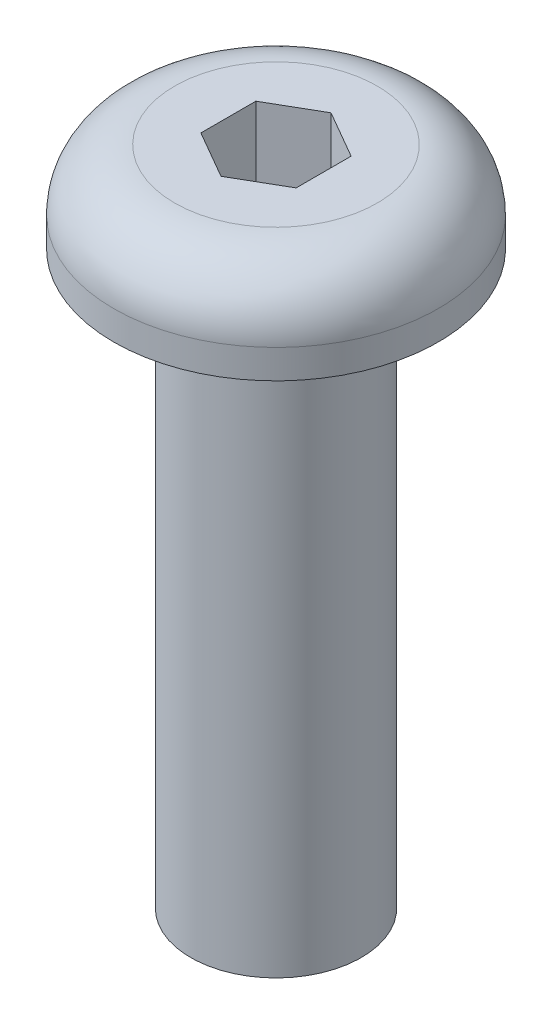
SolidWorks part; units mm, degrees
ref_plane "Front Plane" through (0, 0, 0) normal (0, 0, 1) x (1, 0, 0)
ref_plane "Top Plane" through (0, 0, 0) normal (0, 1, 0) x (1, 0, 0)
ref_plane "Right Plane" through (0, 0, 0) normal (1, 0, 0) x (0, 0, -1)
sketch "Sketch1" plane through (0, 0, 0) normal (0, 1, 0) x (1, 0, 0)
  circle A0 centre (0, 0) radius 1.4224
  dimension "D1" = 2.8448
extrude "Boss-Extrude1" add sketch "Sketch1" along normal blind 9.525
sketch "Sketch2" plane through (0, 9.525, 0) normal (0, 1, 0) x (1, 0, 0)
  circle A0 centre (0, 0) radius 2.7051
  dimension "D1" = 5.4102
extrude "Boss-Extrude2" add sketch "Sketch2" along normal blind 1.4986
fillet "Fillet1" radius 1.016 1 edges at (0, 11.0236, 2.7051)
sketch "Sketch3" plane through (0, 11.0236, 0) normal (0, 1, 0) x (1, 0, 0)
  line L1 (0, 0.9165) -> (-0.7937, 0.4583)
  line L2 (-0.7937, 0.4583) -> (-0.7937, -0.4583)
  line L3 (-0.7937, -0.4583) -> (0, -0.9165)
  line L4 (0, -0.9165) -> (0.7938, -0.4583)
  line L5 (0.7938, -0.4583) -> (0.7938, 0.4583)
  line L6 (0.7938, 0.4583) -> (0, 0.9165)
  circle A0 centre (0, 0) radius 0.7937 construction
  dimension "D1" = 1.5875
extrude "Cut-Extrude1" cut sketch "Sketch3" against normal blind 2.3813
